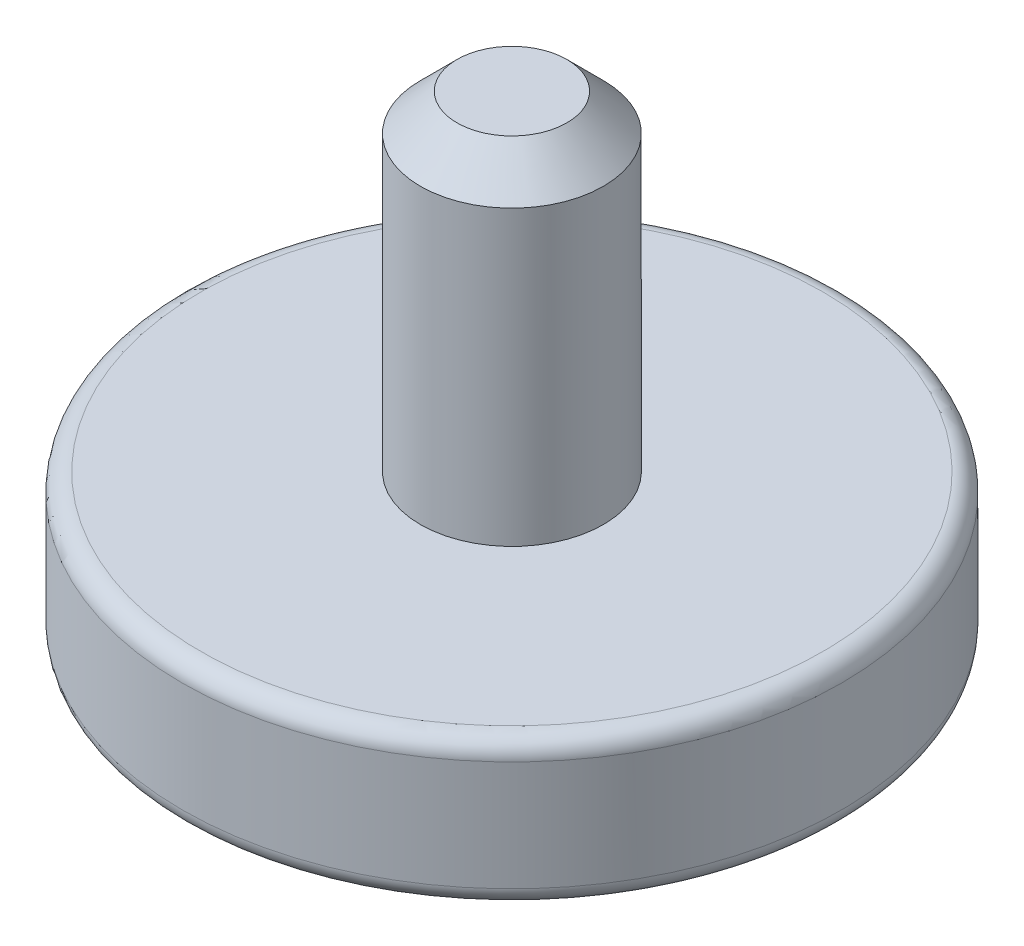
SolidWorks part; units mm, degrees
ref_plane "Front Plane" through (0, 0, 0) normal (0, 0, 1) x (1, 0, 0)
ref_plane "Top Plane" through (0, 0, 0) normal (0, 1, 0) x (1, 0, 0)
ref_plane "Right Plane" through (0, 0, 0) normal (1, 0, 0) x (0, 0, -1)
sketch "Sketch1" plane through (0, 0, 0) normal (0, 0, 1) x (1, 0, 0)
  line L0 (0, 8.13) -> (0, -7.59) construction
  line L1 (0, 0) -> (1.75, 0)
  line L2 (1.75, 0) -> (1.75, 1.5)
  line L3 (1.75, 1.5) -> (1.25, 1.5)
  line L4 (1.25, 1.5) -> (1.25, 4.5)
  line L5 (1.25, 4.5) -> (9, 4.5)
  line L6 (9, 4.5) -> (9, 8.5)
  line L7 (9, 8.5) -> (2.5, 8.5)
  line L8 (2.5, 8.5) -> (2.5, 17.5)
  line L9 (2.5, 17.5) -> (0, 17.5)
  line L10 (0, 17.5) -> (0, 0)
  point P14 (0.875, 0)
  dimension "D1" = 2.5
  dimension "D2" = 3.5
  dimension "D3" = 18
  dimension "D4" = 4
  dimension "D5" = 9
  dimension "D6" = 4.5
  dimension "D7" = 1.5
  dimension "D8" = 5
revolve "Revolve1" add sketch "Sketch1" angle 360 about L0
fillet "Fillet4" radius 0.5 2 edges at (0, 4.5, 9) (0, 8.5, 9)
chamfer "Chamfer1" distance 1 angle 45 1 edges at (0, 17.5, 2.5)
fillet "Fillet6" radius 0.75 2 edges at (0, 1.5, 1.75) (0, 0, 1.75)
